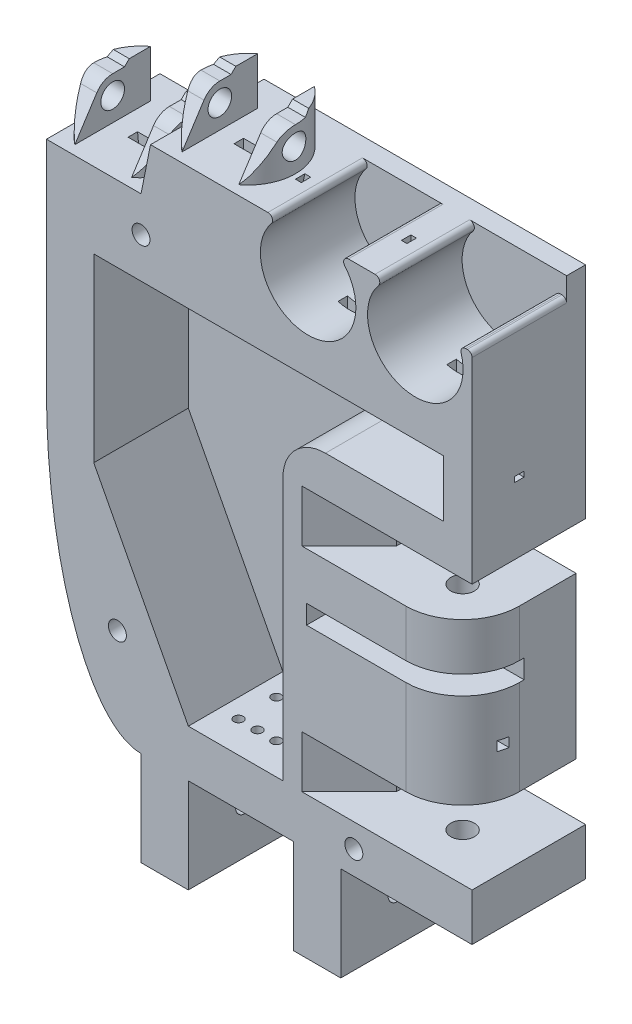
SolidWorks part; units mm, degrees
ref_plane "Front Plane" through (0, 0, 0) normal (0, 0, 1) x (1, 0, 0)
ref_plane "Top Plane" through (0, 0, 0) normal (0, 1, 0) x (1, 0, 0)
ref_plane "Right Plane" through (0, 0, 0) normal (1, 0, 0) x (0, 0, -1)
sketch "Sketch2" plane through (0, 0, 0) normal (0, 0, 1) x (1, 0, 0)
  line L1 (0, 0) -> (114.3, 0)
  line L2 (0, 0) -> (0, 142.875)
  line L3 (0, 142.875) -> (114.3, 142.875)
  line L4 (114.3, 0) -> (114.3, 142.875)
  dimension "D1" = 114.3
  dimension "D2" = 142.875
extrude "Boss-Extrude2" add sketch "Sketch2" along normal blind 30.48 contours L3 L4 L1 L2
fillet "Fillet1" radius 71.501 1 edges at (0, 0, 15.24) second distance 25.4 first distance on face at (0, 71.4375, 15.24)
sketch "Sketch3" plane through (0, 142.875, 0) normal (0, 1, 0) x (1, 0, 0)
  line L0 (0, -30.48) -> (114.3, -30.48) construction
  line L1 (33.8666, -7.62) -> (33.8666, -27.94)
  line L10 (0, -30.48) -> (0, 0) construction
  line L13 (49.1066, -7.62) -> (49.1066, -27.94)
  arc A8 (33.8666, -7.62) -> (33.8666, -27.94) centre (41.4866, -17.78) ccw
  arc A9 (49.1066, -27.94) -> (49.1066, -7.62) centre (41.4866, -17.78) ccw
  dimension "D1" = 25.4
  dimension "D2" = 12.7
  dimension "D3" = 41.4866
  dimension "D5" = 7.62
  dimension "D6" = 7.62
extrude "Boss-Extrude3" add sketch "Sketch3" along normal blind 11.43
sketch "Sketch5" plane through (0, 0, 30.48) normal (0, 0, 1) x (1, 0, 0)
  line L0 (62.6533, 142.875) -> (77.8933, 142.875)
  line L1 (0, 142.875) -> (114.3, 142.875) construction
  line L2 (0, 71.501) -> (0, 142.875) construction
  line L3 (114.3, 0) -> (114.3, 142.875) construction
  line L4 (91.44, 142.875) -> (106.68, 142.875)
  arc A0 (62.6533, 142.875) -> (77.8933, 142.875) centre (70.2733, 132.5567) ccw
  arc A1 (91.44, 142.875) -> (106.68, 142.875) centre (99.06, 132.5567) ccw
  dimension "D1" = 25.654
  dimension "D5" = 25.654
  dimension "D2" = 15.24
  dimension "D3" = 0
  dimension "D4" = 70.2733
  dimension "D6" = 15.24
  dimension "D7" = 15.24
extrude "Cut-Extrude2" cut sketch "Sketch5" against normal blind 25.4
fillet "Fillet2" radius 1.27 3 edges at (91.44, 142.875, 17.78) (77.8933, 142.875, 17.78) (62.6533, 142.875, 17.78)
sketch "Sketch7" plane through (0, 142.875, 0) normal (0, 1, 0) x (1, 0, 0)
  line L0 (0, -30.48) -> (59.4635, -30.48) construction
  line L1 (0, 0) -> (27.94, 0)
  line L2 (0, 0) -> (0, -30.48)
  line L3 (0, -30.48) -> (27.94, -30.48)
  line L4 (27.94, 0) -> (27.94, -30.48)
  dimension "D1" = 27.94
extrude "Cut-Extrude4" cut sketch "Sketch7" against normal blind 12.7
sketch "Sketch8" plane through (0, 130.175, 0) normal (0, 1, 0) x (1, 0, 0)
  line L6 (0, -30.48) -> (27.94, -30.48) construction
  line L7 (0, 0) -> (0, -30.48) construction
  line L8 (5.08, -7.62) -> (5.08, -27.94)
  line L9 (20.32, -7.62) -> (20.32, -27.94)
  arc A4 (5.08, -7.62) -> (5.08, -27.94) centre (12.7, -17.78) ccw
  arc A5 (20.32, -27.94) -> (20.32, -7.62) centre (12.7, -17.78) ccw
  dimension "D1" = 25.4
  dimension "D2" = 12.7
  dimension "D3" = 12.7
  dimension "D4" = 7.62
  dimension "D5" = 7.62
extrude "Boss-Extrude4" add sketch "Sketch8" along normal blind 11.43
sketch "Sketch10" plane through (0, 0, 30.48) normal (0, 0, 1) x (1, 0, 0)
  line L0 (114.3, 0) -> (114.3, 142.875) construction
  line L1 (63.5, 109.855) -> (12.7, 109.855)
  line L3 (63.5, 12.7) -> (38.1, 12.7)
  line L4 (12.7, 109.855) -> (12.7, 61.2775)
  line L5 (0, 71.501) -> (0, 130.175) construction
  line L6 (25.4, 0) -> (114.3, 0) construction
  line L7 (27.94, 142.875) -> (59.4635, 142.875) construction
  line L8 (12.7, 61.2775) -> (38.1, 12.7)
  line L14 (63.5, 94.615) -> (63.5, 12.7)
  line L15 (63.5, 109.855) -> (106.68, 109.855)
  line L17 (63.5, 94.615) -> (106.68, 94.615)
  line L18 (106.68, 109.855) -> (106.68, 94.615)
  dimension "D1" = 7.62
  dimension "D2" = 12.7
  dimension "D3" = 12.7
  dimension "D4" = 33.02
  dimension "D5" = 15.24
extrude "Cut-Extrude6" cut sketch "Sketch10" against normal blind 25.4
sketch "Sketch11" plane through (49.1066, 0, 0) normal (-1, 0, 0) x (0, 0, 1)
  line L0 (7.62, 154.305) -> (27.94, 154.305) construction
  line L1 (27.94, 154.305) -> (27.94, 142.875) construction
  line L2 (27.94, 154.305) -> (7.62, 154.305) construction
  line L3 (22.0449, 151.9849) -> (27.94, 142.875)
  line L4 (27.94, 142.875) -> (27.94, 154.305)
  line L5 (27.94, 154.305) -> (17.78, 154.305)
  circle A0 centre (17.78, 149.225) radius 3.175
  arc A1 (17.78, 154.305) -> (22.0449, 151.9849) centre (17.78, 149.225) cw
  dimension "D2" = 6.35
  dimension "D1" = 5.08
  dimension "D3" = 10.16
extrude "Cut-Extrude7" cut sketch "Sketch11" against normal through all both and the other way through all
sketch "Sketch12" plane through (20.32, 0, 0) normal (-1, 0, 0) x (0, 0, 1)
  line L0 (27.94, 141.605) -> (27.94, 130.175) construction
  line L1 (7.62, 141.605) -> (27.94, 141.605) construction
  line L2 (27.94, 141.605) -> (7.62, 141.605) construction
  line L3 (22.0449, 139.2849) -> (27.94, 130.175)
  line L4 (27.94, 130.175) -> (27.94, 141.605)
  line L5 (27.94, 141.605) -> (17.78, 141.605)
  circle A0 centre (17.78, 136.525) radius 3.175
  arc A1 (17.78, 141.605) -> (22.0449, 139.2849) centre (17.78, 136.525) cw
  dimension "D1" = 6.35
  dimension "D2" = 10.16
  dimension "D3" = 5.08
extrude "Cut-Extrude8" cut sketch "Sketch12" against normal up to surface (7.62 mm away) and the other way through all up to face at (27.94, 136.525, 15.24)
chamfer "Chamfer1" distance 12.7 distance2 2.54 1 edges at (27.94, 130.175, 15.24) first distance on face at (27.94, 136.525, 15.24)
sketch "Sketch13" plane through (0, 0, 30.48) normal (0, 0, 1) x (1, 0, 0)
  line L1 (114.3, 142.875) -> (106.68, 142.875)
  line L2 (114.3, 142.875) -> (114.3, 137.795)
  line L3 (114.3, 137.795) -> (106.68, 137.795)
  line L4 (106.68, 142.875) -> (106.68, 137.795)
  dimension "D1" = 7.62
  dimension "D2" = 5.08
extrude "Cut-Extrude9" cut sketch "Sketch13" against normal up to surface (25.4 mm away) up to face at (95.8158, 134.9459, 5.08)
fillet "Fillet4" radius 1.27 2 edges at (114.3, 137.795, 17.78) (110.7686, 137.795, 17.78)
sketch "Sketch14" plane through (0, 0, 30.48) normal (0, 0, 1) x (1, 0, 0)
  line L0 (114.3, 0) -> (114.3, 136.525) construction
  line L1 (114.3, 12.7) -> (81.28, 12.7)
  line L2 (114.3, 12.7) -> (114.3, 83.82)
  line L3 (114.3, 83.82) -> (81.28, 83.82)
  line L4 (81.28, 12.7) -> (81.28, 26.67)
  line L5 (25.4, 0) -> (114.3, 0) construction
  line L6 (81.28, 69.85) -> (81.28, 83.82)
  line L7 (81.28, 69.85) -> (111.76, 69.85)
  line L9 (81.28, 26.67) -> (111.76, 26.67)
  line L10 (111.76, 69.85) -> (111.76, 26.67)
  dimension "D1" = 12.7
  dimension "D2" = 71.12
  dimension "D3" = 33.02
  dimension "D4" = 13.97
  dimension "D5" = 13.97
  dimension "D6" = 30.48
extrude "Cut-Extrude10" cut sketch "Sketch14" against normal through all
chamfer "Chamfer2" distance 12.7 distance2 12.7 2 edges at (81.28, 19.685, 30.48) (81.28, 76.835, 30.48)
sketch "Sketch15" plane through (0, 0, 0) normal (0, -1, 0) x (1, 0, 0)
  line L0 (114.3, 30.48) -> (114.3, 0) construction
  line L1 (25.4, 30.48) -> (114.3, 30.48) construction
  circle A0 centre (99.06, 17.78) radius 3.175
  dimension "D1" = 6.35
  dimension "D2" = 15.24
  dimension "D3" = 12.7
extrude "Cut-Extrude11" cut sketch "Sketch15" against normal up to surface (109.855 mm away) up to face at (59.69, 109.855, 17.78)
sketch "Sketch16" plane through (0, 141.605, 0) normal (0, 1, 0) x (1, 0, 0)
  line L0 (0.407, -14.5906) -> (5.08, -14.605)
  line L1 (5.08, -14.605) -> (5.08, -7.62)
  line L2 (20.32, -14.605) -> (24.9967, -14.605)
  line L3 (20.32, -7.62) -> (20.32, -17.78) construction
  line L4 (20.32, -7.62) -> (20.32, -14.605)
  arc A0 (24.9967, -14.605) -> (20.32, -7.62) centre (12.7, -17.78) ccw
  arc A1 (5.08, -7.62) -> (0.407, -14.5906) centre (12.7, -17.78) ccw
extrude "Boss-Extrude5" add sketch "Sketch16" along normal blind 1.27
chamfer "Chamfer3" distance 1.27 angle 45 2 edges at (22.6584, 142.875, 14.605) (2.7435, 142.875, 14.5978)
sketch "Sketch17" plane through (0, 154.305, 0) normal (0, 1, 0) x (1, 0, 0)
  line L0 (29.1505, -14.7614) -> (33.8666, -14.7614)
  line L1 (33.8666, -17.78) -> (33.8666, -7.62) construction
  line L2 (33.8666, -14.7614) -> (33.8666, -7.62)
  line L4 (49.1066, -14.7614) -> (53.8226, -14.7614)
  line L5 (49.1066, -7.62) -> (49.1066, -17.78) construction
  line L6 (49.1066, -7.62) -> (49.1066, -14.7614)
  arc A0 (33.8666, -7.62) -> (29.1505, -14.7614) centre (41.4866, -17.78) ccw
  arc A1 (53.8226, -14.7614) -> (49.1066, -7.62) centre (41.4866, -17.78) ccw
extrude "Boss-Extrude6" add sketch "Sketch17" along normal blind 1.27
chamfer "Chamfer4" distance 1.27 angle 45 2 edges at (51.4646, 155.575, 14.7614) (31.5086, 155.575, 14.7614)
fillet "Fillet5" radius 15.24 1 edges at (111.76, 48.26, 30.48)
sketch "Sketch19" plane through (0, 0, 30.48) normal (0, 0, 1) x (1, 0, 0)
  line L0 (111.76, 69.85) -> (111.76, 26.67) construction
  line L1 (81.28, 52.07) -> (111.76, 52.07)
  line L3 (81.28, 57.15) -> (111.76, 57.15)
  line L4 (111.76, 52.07) -> (111.76, 57.15)
  line L5 (81.28, 52.07) -> (111.76, 57.15) construction
  line L6 (81.28, 57.15) -> (111.76, 52.07) construction
  line L7 (68.58, 69.85) -> (96.52, 69.85) construction
  line L9 (81.28, 57.15) -> (69.85, 57.15)
  line L11 (81.28, 52.07) -> (69.85, 52.07)
  line L12 (69.85, 57.15) -> (69.85, 52.07)
  point P0 (96.52, 54.61)
  dimension "D1" = 15.24
  dimension "D2" = 5.08
  dimension "D3" = 12.7
  dimension "D4" = 11.43
extrude "Cut-Extrude12" cut sketch "Sketch19" against normal blind 16.51
sketch "Sketch20" plane through (63.5, 0, 0) normal (-1, 0, 0) x (0, 0, 1)
  line L0 (30.48, 12.7) -> (30.48, 94.615) construction
  line L1 (17.78, 40.64) -> (20.32, 40.64)
  line L2 (17.78, 40.64) -> (17.78, 38.1)
  line L3 (17.78, 38.1) -> (20.32, 38.1)
  line L4 (20.32, 40.64) -> (20.32, 38.1)
  line L5 (5.08, 12.7) -> (30.48, 12.7) construction
  dimension "D1" = 2.54
  dimension "D2" = 2.54
  dimension "D3" = 12.7
  dimension "D4" = 25.4
extrude "Cut-Extrude13" cut sketch "Sketch20" against normal through all
fillet "Fillet6" radius 1.27 1 edges at (63.5, 38.1, 19.05)
ref_plane "Plane1" through (0, 0, 17.78) normal (0, 0, 1) x (1, 0, 0)
sketch "Sketch21" plane through (0, 0, 17.78) normal (0, 0, 1) x (1, 0, 0)
  line L0 (12.7, 109.855) -> (10.4859, 130.175)
  line L1 (0, 130.175) -> (25.4, 130.175) construction
  line L2 (10.4859, 130.175) -> (15.5659, 130.175)
  line L3 (15.5659, 130.175) -> (17.78, 109.855)
  line L4 (106.68, 109.855) -> (12.7, 109.855) construction
  line L5 (17.78, 109.855) -> (12.7, 109.855)
  line L6 (55.4297, 142.875) -> (50.8604, 121.6537)
  line L7 (27.94, 142.875) -> (59.4635, 142.875) construction
  line L8 (38.9466, 142.875) -> (44.0266, 142.875)
  line L9 (38.9466, 142.875) -> (38.9466, 109.855)
  line L10 (38.9466, 109.855) -> (44.0266, 109.855)
  line L11 (44.0266, 142.875) -> (44.0266, 109.855)
  line L12 (33.8666, 151.9849) -> (33.8666, 142.875) construction
  line L13 (50.8604, 121.6537) -> (50.8604, 109.855)
  line L14 (66.8866, 120.1849) -> (71.9666, 120.1849)
  line L15 (66.8866, 120.1849) -> (66.8866, 109.855)
  line L16 (66.8866, 109.855) -> (71.9666, 109.855)
  line L17 (71.9666, 120.1849) -> (71.9666, 109.855)
  line L18 (96.0966, 120.0767) -> (101.1766, 120.0767)
  line L19 (96.0966, 120.0767) -> (96.0966, 109.855)
  line L20 (96.0966, 109.855) -> (101.1766, 109.855)
  line L21 (101.1766, 120.0767) -> (101.1766, 109.855)
  line L22 (50.8604, 109.855) -> (52.4497, 109.855)
  line L23 (52.4497, 109.855) -> (52.4497, 121.6537)
  line L24 (52.4497, 121.6537) -> (57.0191, 142.875)
  line L25 (57.0191, 142.875) -> (55.4297, 142.875)
  line L36 (106.68, 94.615) -> (106.68, 109.855) construction
  line L37 (106.68, 103.1464) -> (114.3, 103.1464)
  line L38 (106.68, 103.1464) -> (106.68, 101.7444)
  line L39 (106.68, 101.7444) -> (114.3, 101.7444)
  line L40 (114.3, 103.1464) -> (114.3, 101.7444)
  line L41 (114.3, 83.82) -> (114.3, 136.525) construction
  line L42 (81.0832, 142.875) -> (88.2501, 142.875) construction
  line L43 (83.8937, 142.875) -> (85.379, 142.875)
  line L44 (83.8937, 142.875) -> (83.8937, 109.855)
  line L45 (83.8937, 109.855) -> (85.379, 109.855)
  line L46 (85.379, 142.875) -> (85.379, 109.855)
  arc A0 (60.4373, 140.7898) -> (80.1093, 140.7898) centre (70.2733, 132.5567) ccw construction
  arc A1 (89.224, 140.7898) -> (111.3683, 136.1675) centre (99.06, 132.5567) ccw construction
  point P9 (13.0259, 130.175)
  dimension "D1" = 5.08
  dimension "D2" = 2.5251
  dimension "D3" = 5.08
  dimension "D4" = 5.08
  dimension "D5" = 5.08
  dimension "D6" = 22.86
  dimension "D7" = 5.08
  dimension "D8" = 24.13
extrude "Cut-Extrude14" cut sketch "Sketch21" against normal blind 1.27 and the other way blind 1.27
fillet "Fillet7" radius 11.43 1 edges at (63.5, 94.615, 17.78)
sketch "Sketch22" plane through (0, 12.7, 0) normal (0, 1, 0) x (1, 0, 0)
  line L0 (38.1, -5.08) -> (38.1, -30.48) construction
  circle A0 centre (43.18, -11.9083) radius 1.27
  circle A1 centre (48.26, -11.9083) radius 1.27
  circle A2 centre (53.34, -11.9083) radius 1.27
  circle A3 centre (58.42, -11.9083) radius 1.27
  circle A4 centre (43.18, -22.0683) radius 1.27
  circle A5 centre (48.26, -22.0683) radius 1.27
  circle A6 centre (53.34, -22.0683) radius 1.27
  circle A7 centre (58.42, -22.0683) radius 1.27
  point P20 (48.694, -11.8615)
  dimension "D1" = 2.54
  dimension "D2" = 2.54
  dimension "D3" = 2.54
  dimension "D4" = 2.54
  dimension "D5" = 2.54
  dimension "D6" = 2.54
  dimension "D7" = 2.54
  dimension "D8" = 2.54
  dimension "D9" = 10.16
  dimension "D10" = 10.16
  dimension "D11" = 10.16
  dimension "D12" = 10.16
  dimension "D13" = 5.08
  dimension "D14" = 5.08
  dimension "D15" = 5.08
  dimension "D16" = 5.08
extrude "Cut-Extrude15" cut sketch "Sketch22" against normal up to surface (12.7 mm away) up to face at (99.06, 0, 14.605)
sketch "Sketch23" plane through (0, 0, 0) normal (0, 0, -1) x (-1, 0, 0)
  line L0 (0, 71.501) -> (0, 130.175) construction
  line L1 (-25.4, 0) -> (-114.3, 0) construction
  circle A0 centre (-25.4, 120.65) radius 2.413
  circle A1 centre (-19.05, 25.4) radius 2.413
  circle A2 centre (-82.55, 6.35) radius 2.413
  dimension "D1" = 4.826
  dimension "D4" = 4.826
  dimension "D9" = 4.826
  dimension "D2" = 25.4
  dimension "D3" = 120.65
  dimension "D5" = 19.05
  dimension "D6" = 25.4
  dimension "D7" = 6.35
  dimension "D8" = 82.55
extrude "Cut-Extrude16" cut sketch "Sketch23" against normal through all both and the other way through all
sketch "Sketch24" plane through (0, 0, 0) normal (0, -1, 0) x (1, 0, 0)
  line L0 (25.4, 0) -> (114.3, 0) construction
  line L1 (25.4, 30.48) -> (38.1, 30.48)
  line L2 (25.4, 30.48) -> (25.4, 0)
  line L3 (25.4, 0) -> (38.1, 0)
  line L4 (38.1, 30.48) -> (38.1, 0)
  line L5 (25.4, 30.48) -> (114.3, 30.48) construction
  line L6 (66.3452, 30.48) -> (79.0452, 30.48)
  line L7 (66.3452, 30.48) -> (66.3452, 0)
  line L8 (66.3452, 0) -> (79.0452, 0)
  line L9 (79.0452, 30.48) -> (79.0452, 0)
  dimension "D1" = 12.7
  dimension "D2" = 12.7
extrude "Boss-Extrude7" add sketch "Sketch24" along normal blind 25.4
sketch "Sketch25" plane through (79.0452, 0, 0) normal (1, 0, 0) x (0, 0, -1)
  line L0 (-30.48, -25.4) -> (0, -25.4) construction
  line L1 (0, -25.4) -> (0, 0) construction
  circle A0 centre (-15.24, -12.7) radius 2.54
  dimension "D3" = 5.08
  dimension "D1" = 12.7
  dimension "D2" = 15.24
extrude "Cut-Extrude17" cut sketch "Sketch25" against normal through all
